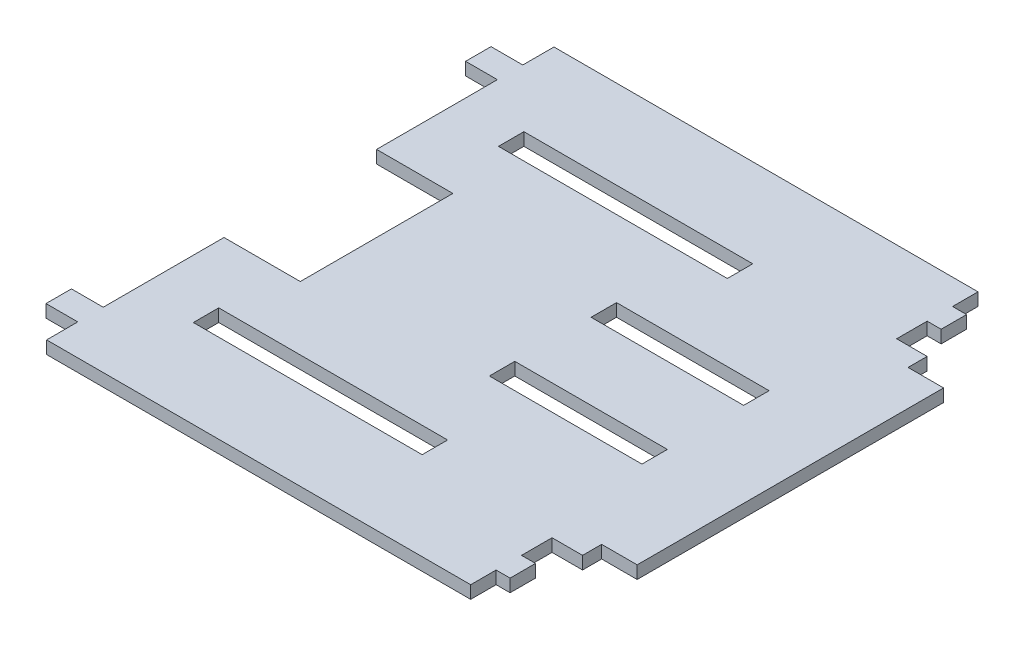
SolidWorks part; units mm, degrees
ref_plane "Alzado" through (0, 0, 0) normal (0, 0, 1) x (1, 0, 0)
ref_plane "Planta" through (0, 0, 0) normal (0, 1, 0) x (1, 0, 0)
ref_plane "Vista lateral" through (0, 0, 0) normal (1, 0, 0) x (0, 0, -1)
sketch "Croquis2" plane through (0, 0, 0) normal (0, 1, 0) x (1, 0, 0)
  line L0 (-81.5023, 77) -> (-92.5023, 77) construction
  line L1 (-92.5023, 77) -> (-92.5023, 88) construction
  line L2 (-92.5023, 88) -> (-81.5023, 88) construction
  line L3 (-81.5023, 97.5) -> (-81.5023, 88) construction
  line L4 (-129.5023, 97.5) -> (-81.5023, 97.5) construction
  line L5 (93.2488, 90.2512) -> (93.2488, 79.2512) construction
  line L6 (89.2488, 90.2512) -> (93.2488, 90.2512) construction
  line L7 (89.2488, 99.7512) -> (89.2488, 90.2512) construction
  line L8 (119.2488, 69.7512) -> (119.2488, 99.7512) construction
  line L9 (119.2488, 99.7512) -> (89.2488, 99.7512) construction
  line L10 (-81.5023, 77) -> (-92.5023, 77) construction
  line L11 (-92.5023, 77) -> (-92.5023, 88) construction
  line L12 (-92.5023, 88) -> (-81.5023, 88) construction
  line L13 (-81.5023, 97.5) -> (-81.5023, 88) construction
  line L14 (-129.5023, 97.5) -> (-81.5023, 97.5) construction
  line L15 (93.2488, 90.2512) -> (93.2488, 79.2512) construction
  line L16 (89.2488, 90.2512) -> (93.2488, 90.2512) construction
  line L17 (89.2488, 99.7512) -> (89.2488, 90.2512) construction
  line L18 (119.2488, 69.7512) -> (119.2488, 99.7512) construction
  line L19 (119.2488, 99.7512) -> (89.2488, 99.7512) construction
  line L20 (-222.2523, 0) -> (277.1189, 0) construction
  line L21 (89.2488, 69.7512) -> (99.2488, 69.7512) construction
  line L22 (89.2488, 79.2512) -> (89.2488, 69.7512) construction
  line L23 (93.2488, 79.2512) -> (89.2488, 79.2512) construction
  line L24 (-81.5023, 77) -> (-81.5023, 67.5) construction
  line L25 (89.2488, 69.7512) -> (99.2488, 69.7512) construction
  line L26 (89.2488, 79.2512) -> (89.2488, 69.7512) construction
  line L27 (93.2488, 79.2512) -> (89.2488, 79.2512) construction
  line L28 (-81.5023, 77) -> (-81.5023, 67.5) construction
  line L29 (119.2488, -67.7512) -> (119.2488, 67.7512)
  line L30 (119.2488, 67.7512) -> (87.2488, 67.7512)
  line L31 (87.2488, 67.7512) -> (87.2488, 79.7512)
  line L32 (87.2488, 79.7512) -> (92.7488, 79.7512)
  line L33 (92.7488, 79.7512) -> (92.7488, 89.7512)
  line L34 (92.7488, 89.7512) -> (87.2488, 89.7512)
  line L35 (87.2488, 89.7512) -> (87.2488, 99.7512)
  line L36 (87.2488, 99.7512) -> (-79.5023, 99.7512)
  line L37 (-79.5023, 99.7512) -> (-79.5023, 87.5)
  line L38 (-79.5023, 87.5) -> (-92.0023, 87.5)
  line L39 (-92.0023, 87.5) -> (-92.0023, 77.5)
  line L40 (-92.0023, 77.5) -> (-79.5023, 77.5)
  line L41 (-79.5023, 77.5) -> (-79.5023, 30)
  line L42 (-79.5023, 30) -> (-49.5023, 30)
  line L43 (-49.5023, 30) -> (-49.5023, -30)
  line L44 (-81.5023, -77) -> (-81.5023, -67.5) construction
  line L45 (93.2488, -79.2512) -> (89.2488, -79.2512) construction
  line L46 (89.2488, -79.2512) -> (89.2488, -69.7512) construction
  line L47 (89.2488, -69.7512) -> (99.2488, -69.7512) construction
  line L48 (119.2488, -99.7512) -> (89.2488, -99.7512) construction
  line L49 (119.2488, -69.7512) -> (119.2488, -99.7512) construction
  line L50 (89.2488, -99.7512) -> (89.2488, -90.2512) construction
  line L51 (89.2488, -90.2512) -> (93.2488, -90.2512) construction
  line L52 (93.2488, -90.2512) -> (93.2488, -79.2512) construction
  line L53 (-81.5023, -97.5) -> (-81.5023, -88) construction
  line L54 (-92.5023, -88) -> (-81.5023, -88) construction
  line L55 (-92.5023, -77) -> (-92.5023, -88) construction
  line L56 (-81.5023, -77) -> (-92.5023, -77) construction
  line L57 (-79.5023, -30) -> (-49.5023, -30)
  line L58 (-79.5023, -77.5) -> (-79.5023, -30)
  line L59 (-92.0023, -77.5) -> (-79.5023, -77.5)
  line L60 (-92.0023, -87.5) -> (-92.0023, -77.5)
  line L61 (-79.5023, -87.5) -> (-92.0023, -87.5)
  line L62 (-79.5023, -99.7512) -> (-79.5023, -87.5)
  line L63 (87.2488, -99.7512) -> (-79.5023, -99.7512)
  line L64 (87.2488, -89.7512) -> (87.2488, -99.7512)
  line L65 (92.7488, -89.7512) -> (87.2488, -89.7512)
  line L66 (92.7488, -79.7512) -> (92.7488, -89.7512)
  line L67 (87.2488, -79.7512) -> (92.7488, -79.7512)
  line L68 (87.2488, -67.7512) -> (87.2488, -79.7512)
  line L69 (119.2488, -67.7512) -> (87.2488, -67.7512)
  line L70 (-37.2209, -20) -> (102.5707, -20) construction
  line L71 (-66.264, -60) -> (60.5807, -60) construction
  line L72 (79.8516, 15) -> (19.8516, 15)
  line L73 (79.8516, -25) -> (19.8516, -25)
  line L74 (79.8516, -25) -> (79.8516, -15)
  line L75 (79.8516, -15) -> (19.8516, -15)
  line L76 (19.8516, -25) -> (19.8516, -15)
  line L77 (79.8516, -25) -> (19.8516, -15) construction
  line L78 (79.8516, -15) -> (19.8516, -25) construction
  line L79 (33.4265, -65) -> (-56.5735, -65)
  line L80 (33.4265, -65) -> (33.4265, -55)
  line L81 (33.4265, -55) -> (-56.5735, -55)
  line L82 (-56.5735, -65) -> (-56.5735, -55)
  line L83 (33.4265, -65) -> (-56.5735, -55) construction
  line L84 (33.4265, -55) -> (-56.5735, -65) construction
  line L85 (19.8516, 25) -> (19.8516, 15)
  line L86 (79.8516, 25) -> (19.8516, 25)
  line L87 (79.8516, 25) -> (79.8516, 15)
  line L88 (33.4265, 55) -> (-56.5735, 55)
  line L89 (-56.5735, 65) -> (-56.5735, 55)
  line L90 (33.4265, 65) -> (-56.5735, 65)
  line L91 (33.4265, 65) -> (33.4265, 55)
  point P52 (-49.5023, 0)
  point P65 (119.2488, 0)
  point P68 (49.8516, -20)
  point P73 (-11.5735, -60)
  dimension "D16" = 60
  dimension "D1" = 2
  dimension "D2" = 2
  dimension "D3" = 0.5
  dimension "D4" = 1
  dimension "D5" = 0.5
  dimension "D6" = 2
  dimension "D7" = 2
  dimension "D8" = 0.5
  dimension "D9" = 1
  dimension "D10" = 0.5
  dimension "D11" = 2
  dimension "D12" = 30
  dimension "D13" = 30
  dimension "D14" = 20
  dimension "D15" = 60
  dimension "D17" = 10
  dimension "D18" = 90
  dimension "D19" = 10
extrude "Saliente-Extruir1" add sketch "Croquis2" along normal blind 5
sketch "Croquis3" plane through (0, 0, 0) normal (0, -1, 0) x (1, 0, 0)
  line L7 (89.2488, 69.7512) -> (100.2488, 69.7512) construction
  line L8 (89.2488, -69.7512) -> (100.2488, -69.7512) construction
  line L9 (100.2488, 69.7512) -> (100.2488, 61.25) construction
  line L10 (100.2488, 61.25) -> (114.2126, 61.25) construction
  line L11 (100.2488, -69.7512) -> (100.2488, -61.25) construction
  line L12 (100.2488, -61.25) -> (114.2126, -61.25) construction
  line L13 (114.2126, -61.25) -> (114.2126, 61.25) construction
  line L14 (89.2488, 68.7512) -> (99.2488, 68.7512)
  line L15 (99.2488, 68.7512) -> (99.2488, 60.25)
  line L16 (99.2488, 60.25) -> (113.2126, 60.25)
  line L17 (113.2126, -60.25) -> (113.2126, 60.25)
  line L18 (89.2488, -68.7512) -> (99.2488, -68.7512)
  line L19 (99.2488, -68.7512) -> (99.2488, -60.25)
  line L20 (99.2488, -60.25) -> (113.2126, -60.25)
  line L21 (99.2488, -60.25) -> (114.2126, -60.25) construction
  line L22 (113.2126, -61.25) -> (113.2126, 60.25) construction
  line L23 (89.2488, 68.7512) -> (89.2488, 75.1305)
  line L24 (89.2488, 75.1305) -> (126.7482, 75.1305)
  line L25 (126.7482, 75.1305) -> (126.7482, -74.2656)
  line L26 (126.7482, -74.2656) -> (89.2488, -74.2656)
  line L27 (89.2488, -74.2656) -> (89.2488, -68.7512)
  dimension "D1" = 1
  dimension "D2" = 1
extrude "Cortar-Extruir1" cut sketch "Croquis3" against normal blind 10
